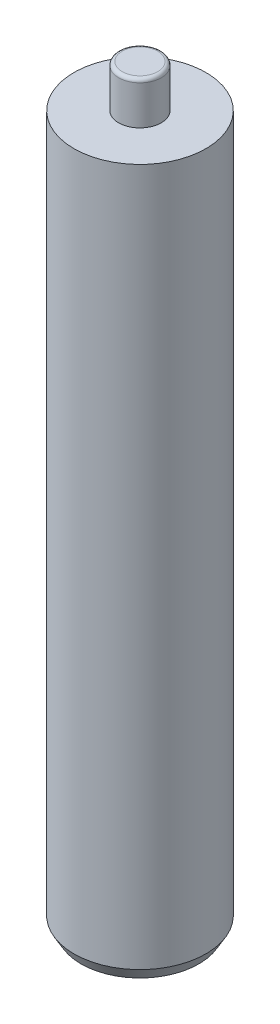
SolidWorks part; units mm, degrees
ref_plane "Front Plane" through (0, 0, 0) normal (0, 0, 1) x (1, 0, 0)
ref_plane "Top Plane" through (0, 0, 0) normal (0, 1, 0) x (1, 0, 0)
ref_plane "Right Plane" through (0, 0, 0) normal (1, 0, 0) x (0, 0, -1)
sketch "Sketch2" plane through (0, 0, 0) normal (0, 1, 0) x (1, 0, 0)
  circle A0 centre (0, 0) radius 9.3
  dimension "D1" = 18.6
extrude "Boss-Extrude1" add sketch "Sketch2" along normal blind 100
sketch "Sketch3" plane through (0, 100, 0) normal (0, 1, 0) x (1, 0, 0)
  circle A0 centre (0, 0) radius 3
extrude "Boss-Extrude2" add sketch "Sketch3" along normal blind 6
chamfer "Chamfer1" distance 1 angle 60 1 edges at (0, 0, 9.3) first distance on face at (0, 0, 9.3)
fillet "Fillet1" radius 0.5 1 edges at (0, 106, 3)
